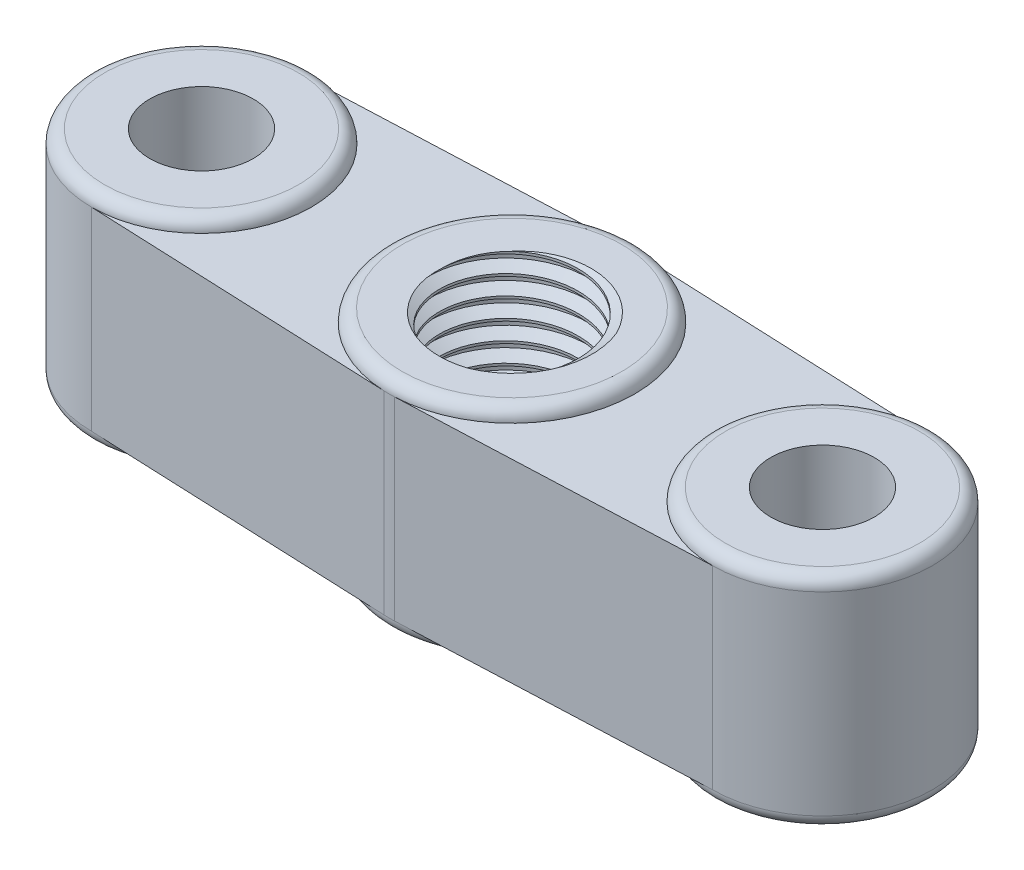
SolidWorks part; units mm, degrees
ref_plane "Front Plane" through (0, 0, 0) normal (0, 0, 1) x (1, 0, 0)
ref_plane "Top Plane" through (0, 0, 0) normal (0, 1, 0) x (1, 0, 0)
ref_plane "Right Plane" through (0, 0, 0) normal (1, 0, 0) x (0, 0, -1)
sketch "Sketch1" plane through (0, 0, 0) normal (0, 1, 0) x (1, 0, 0)
  line L0 (-48, 17) -> (-0.7976, 18.9833)
  line L1 (48, 17) -> (0.7976, 18.9833)
  line L2 (-48, -17) -> (-0.7976, -18.9833)
  line L3 (48, -17) -> (0.7976, -18.9833)
  circle A0 centre (0, 0) radius 10.75
  circle A1 centre (0, 0) radius 19
  circle A2 centre (48, 0) radius 11
  circle A4 centre (48, 0) radius 17
  circle A5 centre (-48, 0) radius 11
  circle A7 centre (-48, 0) radius 17
  circle A8 centre (48, 0) radius 8
  circle A9 centre (-48, 0) radius 8
  dimension "D1" = 21.5
  dimension "D2" = 38
  dimension "D4" = 22
  dimension "D5" = 3
  dimension "D6" = 6
  dimension "D8" = 22
  dimension "D10" = 6
  dimension "D3" = 48
  dimension "D7" = 48
extrude "Boss-Extrude1" add sketch "Sketch1" along normal mid plane 30 contours A7 A5 | A7 L2 A1 L0 | A1 A0 | A4 L1 A1 L3 | A4 A2 region at (-24.9082, 0, 0) region at (-36.3192, 0, -11.6808) region at (0, 0, -18.4626) region at (24.9082, 0, 0) region at (59.6808, 0, -11.6808)
extrude "Boss-Extrude2" add sketch "Sketch1<5>" along normal mid plane 34 contours A4 A2 | A1 A0 | A7 A5 region at (-36.3192, 0, -11.6808) region at (0, 0, -18.4626) region at (59.6808, 0, -11.6808)
sketch "Sketch1<5>" plane through (0, 0, 0) normal (0, 1, 0) x (1, 0, 0) same geometry as "Sketch1"
extrude "Boss-Extrude3" add sketch "Sketch1<6>" along normal up to surface (17 mm away) contours A5 A9 | A2 A8 region at (37.3111, 0, 0) region at (-58.6889, 0, 0) up to face at (48, 17, 11)
sketch "Sketch1<6>" plane through (0, 0, 0) normal (0, 1, 0) x (1, 0, 0) same geometry as "Sketch1"
thread "Thread1" pitch 3 method cut profile "Thread Profile1" start angle 0, offset 3, length 0, pitch 3, diameter 21.5
ref_plane "Plane1" through (-10.75, 20, 0) normal (0, 0, -1) x (1, 0, 0)
sketch "Thread Profile1" plane through (-10.75, 20, 0) normal (0, 0, -1) x (1, 0, 0)
  line L0 (0, 0) -> (0, 3) construction
  line L11 (0, 0) -> (0, 2.625)
  line L12 (0, 2.625) -> (-1.6238, 1.6875)
  line L13 (-1.6238, 1.6875) -> (-1.6238, 0.9375)
  line L15 (-1.6238, 0.9375) -> (0, 0)
  line L17 (-1.6238, 1.3125) -> (0, 1.3125) construction
  point P2 (0, 0)
  dimension "Pitch" = 3
  dimension "Profile_Angle" = 60
  dimension "Profile_Land" = 0.75
  dimension "Profile_Height" = 1.6238
fillet "Fillet1" radius 2 3 edges at (48, 17, 17) (0, 17, 19) (-48, 17, 17)
fillet "Fillet2" radius 2 3 edges at (-48, -17, 17) (0, -17, 19) (48, -17, 17)
